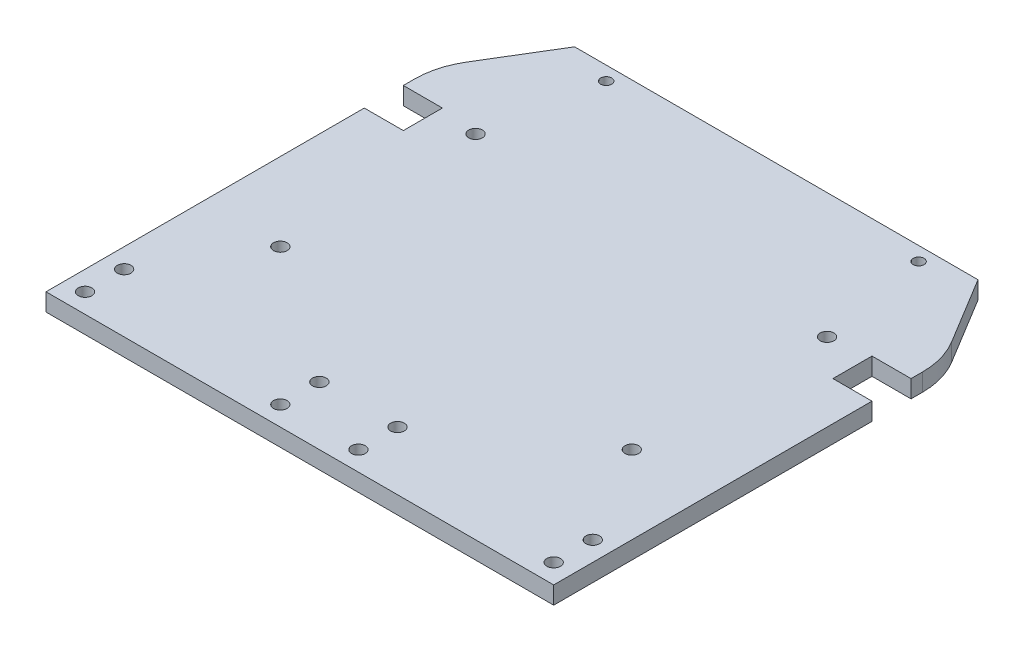
SolidWorks part; units mm, degrees
ref_plane "정면" through (0, 0, 0) normal (0, 0, 1) x (1, 0, 0)
ref_plane "윗면" through (0, 0, 0) normal (0, 1, 0) x (1, 0, 0)
ref_plane "우측면" through (0, 0, 0) normal (1, 0, 0) x (0, 0, -1)
sketch "스케치1" plane through (0, 0, 0) normal (0, 1, 0) x (1, 0, 0)
  line L0 (-65, 25) -> (-51.647, 47)
  line L2 (-65, 25) -> (-65, -75)
  line L3 (-65, -75) -> (65, -75)
  line L4 (65, 25) -> (65, -75)
  line L5 (-51.647, 47) -> (51.647, 47)
  line L7 (65, 25) -> (51.647, 47)
  arc A0 (34.1944, 75.7544) -> (-34.1944, 75.7544) centre (0, 55) ccw construction
  point P0 (0, 0)
  point P4 (0, -75)
  point P11 (0, 95)
  dimension "D2" = 80
  dimension "D4" = 130
  dimension "D1" = 100
  dimension "D3" = 130
  dimension "D5" = 48
extrude "보스-돌출1" add sketch "스케치1" along normal blind 4.5
fillet "필렛1" radius 20 2 edges at (65, 2.25, -25) (-65, 2.25, -25)
sketch "스케치2" plane through (0, 4.5, 0) normal (0, 1, 0) x (1, 0, 0)
  line L0 (-65, 19.4054) -> (-65, -75) construction
  line L1 (-65, 16.5) -> (-55, 16.5)
  line L2 (-65, 16.5) -> (-65, 6.5)
  line L3 (-65, 6.5) -> (-55, 6.5)
  line L4 (-55, 16.5) -> (-55, 6.5)
  line L5 (65, -75) -> (65, 19.4054) construction
  line L6 (65, 16.5) -> (55, 16.5)
  line L7 (65, 16.5) -> (65, 6.5)
  line L8 (65, 6.5) -> (55, 6.5)
  line L9 (55, 16.5) -> (55, 6.5)
  line L10 (-65, -75) -> (65, -75) construction
  dimension "D1" = 10
  dimension "D2" = 10
  dimension "D3" = 81.5
extrude "컷-돌출1" cut sketch "스케치2" against normal through all
sketch "스케치3" plane through (0, 4.5, 0) normal (0, 1, 0) x (1, 0, 0)
  line L0 (-65, -75) -> (65, -75) construction
  line L1 (-60, -70) -> (60, -70) construction
  line L2 (-60, -70) -> (-60, -60) construction
  line L3 (-60, -60) -> (60, -60) construction
  line L4 (60, -70) -> (60, -60) construction
  line L5 (65, -75) -> (65, 6.5) construction
  line L6 (-65, 6.5) -> (-65, -75) construction
  line L7 (-45, 15) -> (45, 15) construction
  line L8 (-10, -60) -> (10, -60) construction
  line L9 (-10, -60) -> (-10, -70) construction
  line L10 (-10, -70) -> (10, -70) construction
  line L11 (10, -60) -> (10, -70) construction
  line L12 (-45, 15) -> (-45, -35) construction
  line L13 (-45, -35) -> (45, -35) construction
  line L14 (45, 15) -> (45, -35) construction
  line L15 (-40, 43.44) -> (40, 43.44) construction
  line L16 (51.647, 47) -> (-51.647, 47) construction
  circle A0 centre (-60, -60) radius 1.75
  circle A1 centre (-60, -70) radius 1.75
  circle A2 centre (60, -60) radius 1.75
  circle A3 centre (60, -70) radius 1.75
  circle A4 centre (-10, -60) radius 1.75
  circle A5 centre (10, -60) radius 1.75
  circle A6 centre (-10, -70) radius 1.75
  circle A7 centre (10, -70) radius 1.75
  circle A8 centre (-45, 15) radius 1.75
  circle A9 centre (45, 15) radius 1.75
  circle A10 centre (-45, -35) radius 1.75
  circle A11 centre (45, -35) radius 1.75
  circle A12 centre (-40, 43.44) radius 1.4
  circle A13 centre (40, 43.44) radius 1.4
  dimension "D7" = 3.5
  dimension "D11" = 3.5
  dimension "D14" = 2.8
  dimension "D15" = 25
  dimension "D1" = 120
  dimension "D2" = 10
  dimension "D3" = 5
  dimension "D4" = 5
  dimension "D5" = 20
  dimension "D6" = 50
  dimension "D8" = 20
  dimension "D9" = 20
  dimension "D10" = 50
  dimension "D12" = 25
  dimension "D13" = 80
  dimension "D16" = 3.56
extrude "컷-돌출2" cut sketch "스케치3" against normal through all
